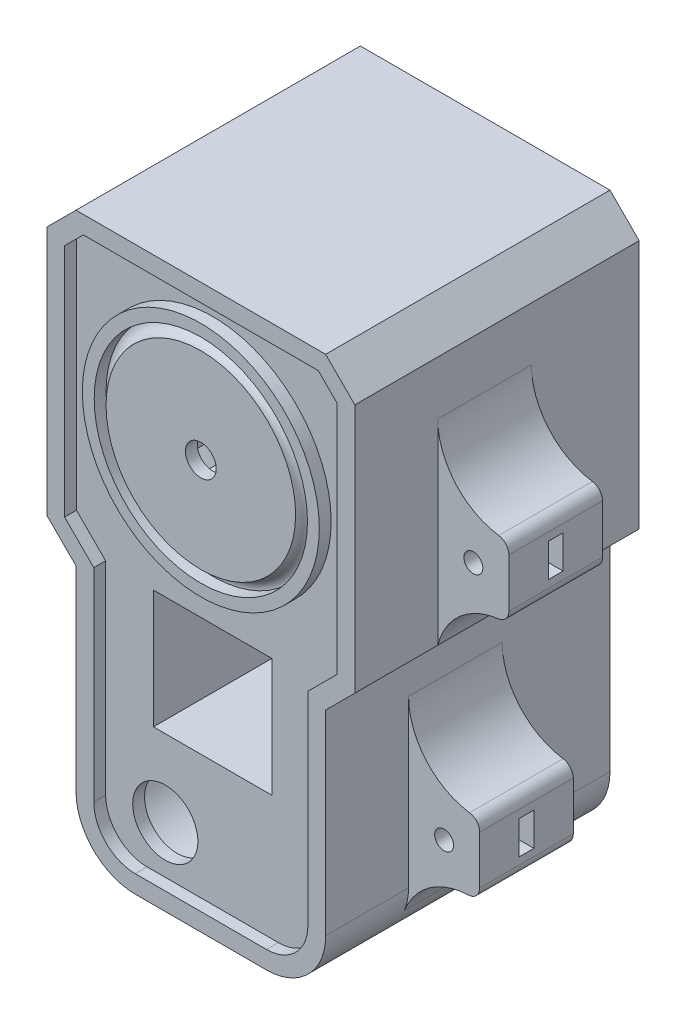
SolidWorks part; units mm, degrees
ref_plane "Alzado" through (0, 0, 0) normal (0, 0, 1) x (1, 0, 0)
ref_plane "Planta" through (0, 0, 0) normal (0, 1, 0) x (1, 0, 0)
ref_plane "Vista lateral" through (0, 0, 0) normal (1, 0, 0) x (0, 0, -1)
sketch "Croquis1" plane through (0, 0, 0) normal (0, 0, 1) x (1, 0, 0)
  line L0 (-19, -21) -> (-21, -19)
  line L1 (19, -21) -> (-19, -21)
  line L2 (21, -19) -> (21, 19)
  line L3 (19, 21) -> (-19, 21)
  line L4 (-21, -19) -> (-21, 19)
  line L5 (21, -21) -> (-21, 21) construction
  line L6 (21, 21) -> (-21, -21) construction
  line L7 (-19, 21) -> (-21, 19)
  line L8 (21, 19) -> (19, 21)
  line L9 (21, -19) -> (19, -21)
  line L10 (26, -21.0711) -> (26, 21.0711)
  line L11 (26, 21.0711) -> (21.0711, 26)
  line L12 (21.0711, 26) -> (-21.0711, 26)
  line L13 (-21.0711, 26) -> (-26, 21.0711)
  line L14 (-26, -21.0711) -> (-26, 21.0711)
  line L15 (-21.0711, -26) -> (-26, -21.0711)
  line L16 (21.0711, -26) -> (-21.0711, -26)
  line L17 (26, -21.0711) -> (21.0711, -26)
  point P0 (0, 0)
  dimension "D1" = 42
  dimension "D2" = 42
  dimension "D3" = 5
extrude "Saliente-Extruir1" add sketch "Croquis1" along normal mid plane 44
sketch "Croquis2" plane through (0, -26, 0) normal (0, -1, 0) x (1, 0, 0)
  line L4 (-21.0711, -22) -> (21.0711, -22)
  line L5 (21.0711, -22) -> (21.0711, 22)
  line L6 (21.0711, 22) -> (-21.0711, 22)
  line L7 (-21.0711, 22) -> (-21.0711, -22)
  line L8 (-21.0711, -22) -> (21.0711, -22)
  line L9 (21.0711, -22) -> (21.0711, 22)
  line L10 (21.0711, 22) -> (-21.0711, 22)
  line L11 (-21.0711, 22) -> (-21.0711, -22)
  dimension "D1" = 0
extrude "Saliente-Extruir2" add sketch "Croquis2" along normal blind 8
sketch "Croquis3" plane through (0, 0, 0) normal (0, 0, 1) x (1, 0, 0)
  line L0 (-19, -21) -> (19, -21) construction
  line L1 (-16.8806, -21) -> (16.8806, -21)
  line L2 (-16.8806, -21) -> (-16.8806, -29)
  line L3 (-16.8806, -29) -> (16.8806, -29)
  line L4 (16.8806, -21) -> (16.8806, -29)
  line L5 (0, 18.4155) -> (0, -35.026) construction
  dimension "D1" = 33.7612
  dimension "D2" = 8
extrude "Cortar-Extruir1" cut sketch "Croquis3" against normal through all contours L2 L1 L4 L3
sketch "Croquis4" plane through (0, 0, 22) normal (0, 0, -1) x (-1, 0, 0)
  line L10 (-26, -21.0711) -> (-21.0711, -26)
  line L11 (-21.0711, -26) -> (-21.0711, -34)
  line L12 (-21.0711, -34) -> (21.0711, -34)
  line L13 (21.0711, -34) -> (21.0711, -26)
  line L14 (21.0711, -26) -> (26, -21.0711)
  line L15 (26, -21.0711) -> (26, 21.0711)
  line L16 (26, 21.0711) -> (21.0711, 26)
  line L17 (21.0711, 26) -> (-21.0711, 26)
  line L18 (-21.0711, 26) -> (-26, 21.0711)
  line L19 (-26, 21.0711) -> (-26, -21.0711)
  line L20 (-26, -21.0711) -> (-21.0711, -26)
  line L21 (-21.0711, -26) -> (-21.0711, -34)
  line L22 (-21.0711, -34) -> (21.0711, -34)
  line L23 (21.0711, -34) -> (21.0711, -26)
  line L24 (21.0711, -26) -> (26, -21.0711)
  line L25 (26, -21.0711) -> (26, 21.0711)
  line L26 (26, 21.0711) -> (21.0711, 26)
  line L27 (21.0711, 26) -> (-21.0711, 26)
  line L28 (-21.0711, 26) -> (-26, 21.0711)
  line L29 (-26, 21.0711) -> (-26, -21.0711)
  circle A0 centre (0, 0) radius 11
  dimension "D2" = 22
  dimension "D1" = 0
extrude "Saliente-Extruir4" add sketch "Croquis4" against normal blind 2
sketch "Croquis7" plane through (0, 0, 24) normal (0, 0, 1) x (1, 0, 0)
  circle A0 centre (0, 0) radius 2.6
  circle A3 centre (0, 0) radius 16
  circle A4 centre (0, 0) radius 16
  dimension "D2" = 5.2
  dimension "D1" = 5
extrude "Saliente-Extruir5" add sketch "Croquis7" along normal blind 2
sketch "Croquis6" plane through (0, -29, 0) normal (0, 1, 0) x (1, 0, 0)
  line L0 (0, -24.5904) -> (0, 23.7869) construction
  line L1 (-14, 18) -> (14, 18)
  line L2 (-14, 18) -> (-14, 6)
  line L3 (-14, 6) -> (14, 6)
  line L4 (14, 18) -> (14, 6)
  dimension "D1" = 28
  dimension "D2" = 12
  dimension "D3" = 18
extrude "Cortar-Extruir3" cut sketch "Croquis6" against normal blind 13
sketch "Croquis8" plane through (0, 0, 0) normal (0, 0, 1) x (1, 0, 0)
  line L0 (-26, -21.0711) -> (-26, 21.0711)
  line L1 (-26, -21.0711) -> (-26, 21.0711)
  line L2 (-26, 21.0711) -> (-21.0711, 26)
  line L3 (-26, 21.0711) -> (-21.0711, 26)
  line L4 (-21.0711, 26) -> (21.0711, 26)
  line L5 (-21.0711, 26) -> (21.0711, 26)
  line L6 (21.0711, 26) -> (26, 21.0711)
  line L7 (21.0711, 26) -> (26, 21.0711)
  line L8 (26, 21.0711) -> (26, -21.0711)
  line L9 (26, 21.0711) -> (26, -21.0711)
  line L10 (26, -21.0711) -> (21.0711, -26)
  line L11 (26, -21.0711) -> (21.0711, -26)
  line L12 (21.0711, -26) -> (21.0711, -34)
  line L13 (21.0711, -26) -> (21.0711, -34)
  line L14 (21.0711, -34) -> (-21.0711, -34)
  line L15 (21.0711, -34) -> (-21.0711, -34)
  line L16 (-21.0711, -34) -> (-21.0711, -26)
  line L17 (-21.0711, -34) -> (-21.0711, -26)
  line L18 (-21.0711, -26) -> (-26, -21.0711)
  line L19 (-21.0711, -26) -> (-26, -21.0711)
  line L20 (0, 0) -> (-39.949, 0) construction
  line L21 (0, 0) -> (0, 31.7363) construction
  line L22 (26, -12) -> (38, -12)
  line L23 (-26, 0) -> (-38, 0)
  line L24 (-26, 0) -> (-26, -12)
  line L25 (-26, -12) -> (-38, -12)
  line L26 (-38, 0) -> (-38, -12)
  line L27 (38, 0) -> (38, -12)
  line L28 (26, 0) -> (38, 0)
  line L29 (26, 0) -> (26, -12)
  line L30 (-38, -12) -> (-26, 0) construction
  circle A0 centre (-32, -6) radius 1.6
  circle A1 centre (32, -6) radius 1.6
  dimension "D3" = 3.2
  dimension "D1" = 12
  dimension "D2" = 12
extrude "Saliente-Extruir6" add sketch "Croquis8" along normal blind 12 and the other way blind 3.8 contours L23 L26 L25 L1 | L28 L9 L22 L27 region at (-32, -11.8303, 0) region at (26.1697, -6, 0)
sketch "Croquis9" plane through (38, 0, 0) normal (1, 0, 0) x (0, 0, -1)
  line L0 (3.8, -6) -> (-12, -6) construction
  line L1 (3.8, 0) -> (3.8, -12) construction
  line L2 (-12, 0) -> (-12, -12) construction
  line L4 (-2.85, -3.2) -> (-5.35, -3.2)
  line L5 (-2.85, -3.2) -> (-2.85, -8.8)
  line L6 (-2.85, -8.8) -> (-5.35, -8.8)
  line L7 (-5.35, -3.2) -> (-5.35, -8.8)
  line L8 (-2.85, -3.2) -> (-5.35, -8.8) construction
  line L9 (-2.85, -8.8) -> (-5.35, -3.2) construction
  point P6 (-4.1, -6)
  dimension "D1" = 5.6
  dimension "D2" = 2.5
extrude "Cortar-Extruir4" cut sketch "Croquis9" against normal blind 10
mirror "Simetría1" about plane through (0, 0, 0) normal (1, 0, 0) of "Cortar-Extruir4"
sketch "Croquis11" plane through (0, -34, 0) normal (0, -1, 0) x (1, 0, 0)
  line L4 (-21.0711, 24) -> (-21.0711, -22)
  line L5 (-21.0711, -22) -> (21.0711, -22)
  line L6 (21.0711, -22) -> (21.0711, 24)
  line L7 (21.0711, 24) -> (-21.0711, 24)
  line L8 (-21.0711, 24) -> (-21.0711, -22)
  line L9 (-21.0711, -22) -> (21.0711, -22)
  line L10 (21.0711, -22) -> (21.0711, 24)
  line L11 (21.0711, 24) -> (-21.0711, 24)
  dimension "D1" = 0
extrude "Saliente-Extruir8" add sketch "Croquis11" along normal blind 35
sketch "Croquis12" plane through (0, 0, -22) normal (0, 0, -1) x (-1, 0, 0)
  line L0 (0, 0) -> (0, -75.996) construction
  line L1 (18.0711, -66) -> (-18.0711, -66)
  line L2 (18.0711, -66) -> (18.0711, -38)
  line L3 (18.0711, -38) -> (-18.0711, -38)
  line L4 (-18.0711, -66) -> (-18.0711, -38)
  line L5 (21.0711, -69) -> (21.0711, -26) construction
  line L6 (21.0711, -69) -> (-21.0711, -69) construction
  dimension "D1" = 3
  dimension "D2" = 3
  dimension "D3" = 28
extrude "Cortar-Extruir5" cut sketch "Croquis12" against normal offset from surface (44 mm away) 2 up to face at (-16, 0, 24)
sketch "Croquis14" plane through (0, 0, 24) normal (0, 0, 1) x (1, 0, 0)
  line L0 (0, 0) -> (0, -70.2297) construction
  line L1 (10, -25) -> (-10, -25)
  line L2 (10, -25) -> (10, -45)
  line L3 (10, -45) -> (-10, -45)
  line L4 (-10, -25) -> (-10, -45)
  line L5 (10, -25) -> (-10, -45) construction
  line L6 (10, -45) -> (-10, -25) construction
  point P0 (0, -35)
  dimension "D1" = 35
  dimension "D2" = 20
  dimension "D3" = 20
extrude "Cortar-Extruir7" cut sketch "Croquis14" against normal blind 25
sketch "Croquis15" plane through (0, 0, 22) normal (0, 0, -1) x (-1, 0, 0)
  line L0 (-10, -38) -> (-18.0711, -38)
  line L1 (-18.0711, -38) -> (-18.0711, -49)
  line L2 (-18.0711, -49) -> (18.0711, -49)
  line L3 (18.0711, -49) -> (18.0711, -38)
  line L4 (18.0711, -38) -> (10, -38)
  line L5 (10, -38) -> (10, -45)
  line L6 (10, -45) -> (-10, -45)
  line L7 (-10, -45) -> (-10, -38)
  dimension "D1" = 4
  dimension "D2" = 90
  dimension "D3" = 90
extrude "Saliente-Extruir9" add sketch "Croquis15" along normal blind 25
sketch "Croquis16" plane through (0, 0, -3) normal (0, 0, -1) x (-1, 0, 0)
  line L1 (-10, -45) -> (10, -45)
  line L2 (-10, -45) -> (-10, -25)
  line L3 (-10, -25) -> (10, -25)
  line L4 (10, -45) -> (10, -25)
extrude "Saliente-Extruir11" add sketch "Croquis16" against normal blind 3.2
sketch "Croquis17" plane through (0, -49, 0) normal (0, -1, 0) x (1, 0, 0)
  line L0 (0, -10) -> (0, 26) construction
  line L1 (16, 26) -> (-16, 26) construction
  circle A0 centre (0, 8) radius 1.6
  point P6 (0, 0)
  dimension "D1" = 3.2
  dimension "D2" = 8
extrude "Cortar-Extruir8" cut sketch "Croquis17" against normal blind 40
sketch "Croquis18" plane through (0, -21, 0) normal (0, 1, 0) x (1, 0, 0)
  circle A0 centre (0, -8) radius 1.6 construction
  circle A1 centre (0, -8) radius 1.6
  circle A2 centre (0, -8) radius 4.8
  dimension "D1" = 3.2
extrude "Cortar-Extruir9" cut sketch "Croquis18" against normal blind 2
sketch "Croquis13" plane through (0, 0, 22) normal (0, 0, -1) x (-1, 0, 0)
  line L0 (18.0711, -52) -> (-18.0711, -52) construction
  line L1 (18.0711, -66) -> (18.0711, -38) construction
  line L2 (-18.0711, -38) -> (-18.0711, -66) construction
  line L3 (0, 0) -> (0, -68.0761) construction
  circle A0 centre (8, -58) radius 5.5
  point P8 (0, 0)
  point P9 (-8.0054, -58.5)
  point P13 (10.141, -58.5)
  dimension "D1" = 11
  dimension "D3" = 11
  dimension "D2" = 6
  dimension "D4" = 8
extrude "Cortar-Extruir6" cut sketch "Croquis13" against normal blind 2
fillet "Redondeo1" radius 10 2 edges at (-18.0711, -66, 0) (18.0711, -66, 0)
fillet "Redondeo2" radius 10 2 edges at (-21.0711, -69, 1) (21.0711, -69, 1)
sketch "Croquis19" plane through (21.0711, 0, 0) normal (1, 0, 0) x (0, 0, -1)
  line L0 (0, 0) -> (0, -69) construction
  line L1 (22, -69) -> (-24, -69) construction
  line L2 (3.8, 0) -> (3.8, -12) construction
  line L3 (3.8, -55) -> (-12, -55)
  line L4 (3.8, -55) -> (3.8, -43)
  line L5 (3.8, -43) -> (-12, -43)
  line L6 (-12, -55) -> (-12, -43)
  line L7 (-12, 0) -> (-12, -12) construction
  line L8 (-2.85, -8.8) -> (-2.85, -3.2) construction
  line L9 (-2.85, -51.8) -> (-5.35, -51.8)
  line L10 (-2.85, -51.8) -> (-2.85, -46.2)
  line L11 (-2.85, -46.2) -> (-5.35, -46.2)
  line L12 (-5.35, -51.8) -> (-5.35, -46.2)
  line L13 (-5.35, -3.2) -> (-5.35, -8.8) construction
  line L14 (3.8, -49) -> (-12, -49) construction
  dimension "D1" = 12
  dimension "D2" = 43
  dimension "D3" = 5.6
extrude "Saliente-Extruir12" add sketch "Croquis19" along normal blind 12
sketch "Croquis20" plane through (0, 0, -3.8) normal (0, 0, -1) x (-1, 0, 0)
  line L0 (-33.0711, -49) -> (-21.0711, -49) construction
  line L1 (-33.0711, -55) -> (-33.0711, -43) construction
  line L2 (-21.0711, -59) -> (-21.0711, -26) construction
  line L3 (-27.0711, -55) -> (-27.0711, -43) construction
  line L4 (-33.0711, -55) -> (-21.0711, -55) construction
  line L5 (-33.0711, -43) -> (-21.0711, -43) construction
  circle A0 centre (-27.0711, -49) radius 1.6
  dimension "D1" = 3.2
extrude "Cortar-Extruir10" cut sketch "Croquis20" against normal through all
mirror "Simetría2" about plane through (0, 0, 0) normal (1, 0, 0) of "Saliente-Extruir12", "Cortar-Extruir10"
fillet "Redondeo3" radius 12 4 edges at (21.0711, -55, 4.1) (26, -12, 4.1) (26, 0, 4.1) (21.0711, -43, 4.1)
fillet "Redondeo4" radius 2 4 edges at (33.0711, -55, 4.1) (33.0711, -43, 4.1) (38, -12, 4.1) (38, 0, 4.1)
fillet "Redondeo5" radius 10 4 edges at (-21.0711, -55, 4.1) (-21.0711, -43, 4.1) (-26, -12, 4.1) (-26, 0, 4.1)
fillet "Redondeo6" radius 2 4 edges at (-33.0711, -43, 4.1) (-38, 0, 4.1) (-38, -12, 4.1) (-33.0711, -55, 4.1)
fillet "Redondeo7" radius 2 1 edges at (-16, 0, 24)
sketch "Croquis22" plane through (0, 0, 24) normal (0, 0, 1) x (1, 0, 0)
  line L20 (-18.0711, -24.7574) -> (-18.0711, -59)
  line L21 (-11.0711, -66) -> (11.0711, -66)
  line L22 (18.0711, -59) -> (18.0711, -24.7574)
  line L23 (18.0711, -24.7574) -> (23, -19.8284)
  line L24 (23, -19.8284) -> (23, 19.8284)
  line L25 (23, 19.8284) -> (19.8284, 23)
  line L26 (19.8284, 23) -> (-19.8284, 23)
  line L27 (-19.8284, 23) -> (-23, 19.8284)
  line L28 (-23, 19.8284) -> (-23, -19.8284)
  line L29 (-23, -19.8284) -> (-18.0711, -24.7574)
  line L30 (-18.0711, -24.7574) -> (-18.0711, -59)
  line L31 (-11.0711, -66) -> (11.0711, -66)
  line L32 (18.0711, -59) -> (18.0711, -24.7574)
  line L33 (18.0711, -24.7574) -> (23, -19.8284)
  line L34 (23, -19.8284) -> (23, 19.8284)
  line L35 (23, 19.8284) -> (19.8284, 23)
  line L36 (19.8284, 23) -> (-19.8284, 23)
  line L37 (-19.8284, 23) -> (-23, 19.8284)
  line L38 (-23, 19.8284) -> (-23, -19.8284)
  line L39 (-23, -19.8284) -> (-18.0711, -24.7574)
  line L40 (-21.0711, -26) -> (-21.0711, -59)
  line L41 (-11.0711, -69) -> (11.0711, -69)
  line L42 (21.0711, -59) -> (21.0711, -26)
  line L43 (21.0711, -26) -> (26, -21.0711)
  line L44 (26, -21.0711) -> (26, 21.0711)
  line L45 (26, 21.0711) -> (21.0711, 26)
  line L46 (21.0711, 26) -> (-21.0711, 26)
  line L47 (-21.0711, 26) -> (-26, 21.0711)
  line L48 (-26, 21.0711) -> (-26, -21.0711)
  line L49 (-26, -21.0711) -> (-21.0711, -26)
  line L50 (-21.0711, -26) -> (-21.0711, -59)
  line L51 (-11.0711, -69) -> (11.0711, -69)
  line L52 (21.0711, -59) -> (21.0711, -26)
  line L53 (21.0711, -26) -> (26, -21.0711)
  line L54 (26, -21.0711) -> (26, 21.0711)
  line L55 (26, 21.0711) -> (21.0711, 26)
  line L56 (21.0711, 26) -> (-21.0711, 26)
  line L57 (-21.0711, 26) -> (-26, 21.0711)
  line L58 (-26, 21.0711) -> (-26, -21.0711)
  line L59 (-26, -21.0711) -> (-21.0711, -26)
  circle A3 centre (0, 0) radius 18 construction
  arc A4 (-18.0711, -59) -> (-11.0711, -66) centre (-11.0711, -59) ccw
  arc A5 (11.0711, -66) -> (18.0711, -59) centre (11.0711, -59) ccw
  arc A6 (-18.0711, -59) -> (-11.0711, -66) centre (-11.0711, -59) ccw
  arc A7 (11.0711, -66) -> (18.0711, -59) centre (11.0711, -59) ccw
  arc A8 (-21.0711, -59) -> (-11.0711, -69) centre (-11.0711, -59) ccw
  arc A9 (11.0711, -69) -> (21.0711, -59) centre (11.0711, -59) ccw
  arc A10 (-21.0711, -59) -> (-11.0711, -69) centre (-11.0711, -59) ccw
  arc A11 (11.0711, -69) -> (21.0711, -59) centre (11.0711, -59) ccw
  circle A12 centre (0, 0) radius 20
  circle A13 centre (0, 0) radius 20
  circle A14 centre (0, 0) radius 18
  circle M26 centre (0, 0) radius 18
  line M32 (-21.0711, -26) -> (-21.0711, -59)
  arc M33 (-21.0711, -59) -> (-11.0711, -69) centre (-11.0711, -59) ccw
  line M34 (-11.0711, -69) -> (11.0711, -69)
  arc M35 (11.0711, -69) -> (21.0711, -59) centre (11.0711, -59) ccw
  line M36 (21.0711, -59) -> (21.0711, -26)
  line M37 (21.0711, -26) -> (26, -21.0711)
  line M38 (26, -21.0711) -> (26, 21.0711)
  line M39 (26, 21.0711) -> (21.0711, 26)
  line M40 (21.0711, 26) -> (-21.0711, 26)
  line M41 (-21.0711, 26) -> (-26, 21.0711)
  line M42 (-26, 21.0711) -> (-26, -21.0711)
  line M43 (-26, -21.0711) -> (-21.0711, -26)
  dimension "D1" = 3
  dimension "D2" = 0
  dimension "D3" = 2
extrude "Saliente-Extruir13" add sketch "Croquis22" along direction (0, 0, 1) on the side of the normal blind 2 contours A7 L31 A6 L30 L39 L38 L37 L36 L35 L34 L33 L32 M43 M32 M33 M34 M35 M36 M37 M38 M39 M40 M41 M42 | A13 M26 region at (-22.7697, -22.7697, 24) region at (-19.4343, 0, 24)
